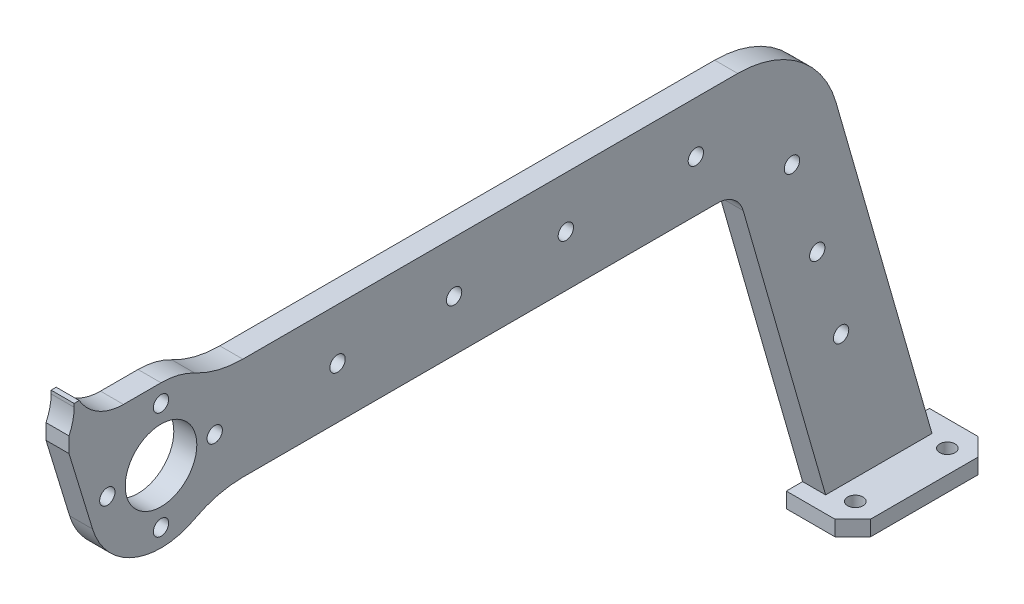
SolidWorks part; units mm, degrees
ref_plane "前视基准面" through (0, 0, 0) normal (0, 0, 1) x (1, 0, 0)
ref_plane "上视基准面" through (0, 0, 0) normal (0, 1, 0) x (1, 0, 0)
ref_plane "右视基准面" through (0, 0, 0) normal (1, 0, 0) x (0, 0, -1)
sketch "草图1" plane through (0, 0, 0) normal (1, 0, 0) x (0, 0, -1)
  line L2 (113.8757, -13.768) -> (130, -70)
  line L3 (130, -70) -> (150.806, -70)
  line L4 (150.806, -70) -> (132.0205, -4.4873)
  line L5 (112.7953, 10) -> (16, 10)
  line L7 (16, -10) -> (108.8754, -10)
  line L8 (140.8126, -71.4286) -> (116.4936, 13.3819) construction
  line L9 (0, 14) -> (-18, 14)
  line L10 (-18, 14) -> (-18, 11)
  line L11 (-18, 11) -> (-13.3889, -4.091)
  arc A0 (6.5882, 12.3529) -> (6.5882, -12.3529) centre (0, 0) ccw
  circle A1 centre (0, 0) radius 10.5 construction
  circle A2 centre (0, 0) radius 7
  circle A3 centre (0, 10.5) radius 1.5
  arc A7 (132.0205, -4.4873) -> (112.7953, 10) centre (112.7953, -10) ccw
  arc A8 (108.8754, -10) -> (113.8757, -13.768) centre (108.8754, -15.2018) cw
  arc A15 (16, 10) -> (6.5882, 12.3529) centre (16, 30) cw
  arc A16 (16, -10) -> (6.5882, -12.3529) centre (16, -30) ccw
  circle A17 centre (10.5, 0) radius 1.5
  circle A18 centre (0, -10.5) radius 1.5
  circle A19 centre (-10.5, 0) radius 1.5
  point P25 (0, 0)
  point P36 (140.403, -70)
  point P43 (9.798, 7.7889)
  point P50 (9.798, -10)
  dimension "D1" = 28
  dimension "D3" = 14
  dimension "D4" = 3
  dimension "D9" = 20
  dimension "D13" = 4
  dimension "D24" = 20
  dimension "D25" = 20
  dimension "D5" = 21
  dimension "D6" = 106
  dimension "D7" = 20
  dimension "D8" = 130
  dimension "D10" = 70
  dimension "D11" = 20
  dimension "D12" = 20.806
  dimension "D21" = 18
  dimension "D22" = 3
extrude "凸台-拉伸1" add sketch "草图1" along normal mid plane 4.5 contours A16 L7 A8 L2 L3 L4 A7 L5 A15 A0 A18 A17 A3 A2 | A0 L9 L10 L11 | A16 A0 region at (0, -9.5702, -113.1192) region at (0, 9.7023, 13.097)
sketch "草图5" plane through (0, -70, 0) normal (0, -1, 0) x (1, 0, 0)
  line L0 (-2.25, -113.8757) -> (-2.25, -130) construction
  line L1 (-2.25, -126.806) -> (10.75, -126.806)
  line L2 (-2.25, -126.806) -> (-2.25, -154.806)
  line L3 (-2.25, -154.806) -> (10.75, -154.806)
  line L4 (10.75, -126.806) -> (10.75, -154.806)
  line L5 (2.25, -150.806) -> (-2.25, -150.806) construction
  point P8 (-2.25, -161.666)
  point P9 (-2.25, -138.666)
  dimension "D1" = 13
  dimension "D2" = 28
  dimension "D3" = 4
extrude "凸台-拉伸3" add sketch "草图5" along normal blind 3
sketch "草图6" plane through (0, -70, 0) normal (0, 1, 0) x (1, 0, 0)
  line L0 (10.75, 140.806) -> (-2.25, 140.806) construction
  line L1 (10.75, 154.806) -> (10.75, 126.806) construction
  line L2 (-2.25, 150.806) -> (-2.25, 132.0205) construction
  line L5 (2.25, 150.806) -> (2.25, 132.0205) construction
  circle A0 centre (6.25, 149.806) radius 1.5
  circle A1 centre (6.25, 131.806) radius 1.5
  point P12 (2.25, 150.806)
  point P14 (16.2278, 141.666)
  dimension "D3" = 3
  dimension "D1" = 9
  dimension "D2" = 4
extrude "切除-拉伸2" cut sketch "草图6" against normal through all
sketch "草图7" plane through (2.25, 0, 0) normal (1, 0, 0) x (0, 0, -1)
  line L1 (0, 14) -> (-18, 14) construction
  line L2 (-17.0011, 14) -> (-17.0011, 18.9987)
  line L3 (-17.0011, 18.9987) -> (-16.0023, 18.9987)
  line L4 (-16.0023, 18.9987) -> (-16.0023, 14)
  line L5 (-16.0023, 14) -> (-17.0011, 14)
extrude "凸台-拉伸4" add sketch "草图7" against normal up to vertex (4.5 mm away) up to point (-2.25, 14, 0)
fillet "圆角1" radius 10 2 edges at (0, 14, 16.0023) (0, 14, 17.0011)
chamfer "倒角1" distance 3.5 angle 45 2 edges at (10.75, -71.5, -126.806) (10.75, -71.5, -154.806)
sketch "草图8" plane through (-2.25, 0, 0) normal (-1, 0, 0) x (0, 0, 1)
  line L0 (-16, 10) -> (-16, -10) construction
  line L1 (-112.7953, 10) -> (-108.8754, -10) construction
  line L2 (-132.0205, -4.4873) -> (-113.8757, -13.768) construction
  line L3 (-127.2436, -60.3874) -> (-146.4689, -54.8746) construction
  line L4 (-113.8757, -13.768) -> (-130, -70) construction
  line L5 (-150.806, -70) -> (-132.0205, -4.4873) construction
  line L6 (-136.8562, -57.631) -> (-122.9481, -9.1276)
  line L7 (-110.8353, 0) -> (-16, 0)
  arc A0 (-108.8754, -10) -> (-113.8757, -13.768) centre (-108.8754, -15.2018) ccw construction
  arc A1 (-122.9481, -9.1276) -> (-110.8353, 0) centre (-110.8353, -12.6009) cw
  dimension "D1" = 10
sketch "草图9" plane through (-2.25, 0, 0) normal (-1, 0, 0) x (0, 0, 1)
  line L0 (-136.8562, -57.631) -> (-122.9481, -9.1276) construction
  line L1 (-110.8353, 0) -> (-16, 0) construction
  point P0 (-133.0265, -44.2751)
  point P1 (-128.362, -28.008)
  point P4 (-104.6157, 0)
  point P5 (-79.1822, 0)
  point P8 (-57.3282, 0)
  point P9 (-34.5323, 0)
  point P10 (-128.362, -28.008)
  point P11 (-123.4152, -10.7566)
  point P12 (-133.0265, -44.2751)
sketch "草图10" plane through (-2.25, 0, 0) normal (-1, 0, 0) x (0, 0, 1)
  circle A0 centre (-34.5323, 0) radius 1.5
  dimension "D1" = 3
extrude "切除-拉伸3" cut sketch "草图10" against normal blind 10
pattern_sketch "草图阵列1" of "切除-拉伸3" driven by "草图9"
